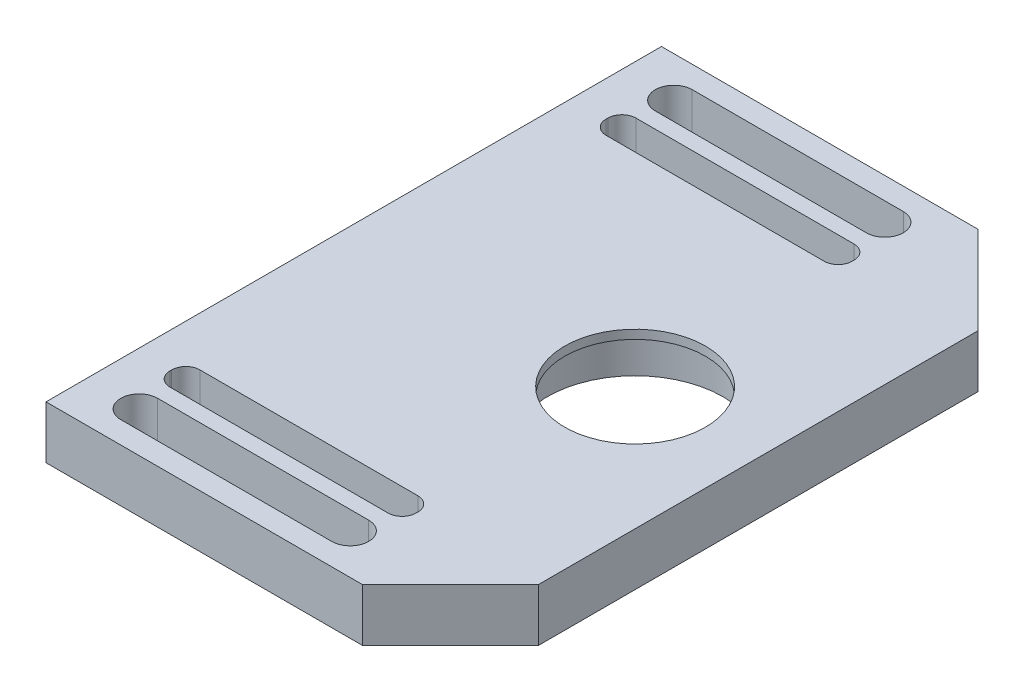
SolidWorks part; units mm, degrees
material "1060 Legierung"
ref_plane "Ebene vorne" through (0, 0, 0) normal (0, 0, 1) x (1, 0, 0)
ref_plane "Ebene oben" through (0, 0, 0) normal (0, 1, 0) x (1, 0, 0)
ref_plane "Ebene rechts" through (0, 0, 0) normal (1, 0, 0) x (0, 0, -1)
sketch "Skizze1" plane through (0, 0, 0) normal (0, 1, 0) x (1, 0, 0)
  line L0 (-9, 0) -> (9, 0) construction
  line L1 (-9, 17.5) -> (9, 17.5)
  line L2 (-9, 17.5) -> (-9, -17.5)
  line L3 (-6, -15.2) -> (6, -15.2) construction
  line L4 (-6, -16.25) -> (6, -16.25)
  line L5 (-6, -14.15) -> (6, -14.15)
  line L6 (-7, 13.25) -> (7, 13.25)
  line L7 (-7, 13.25) -> (-7, 11.55)
  line L8 (-7, 11.55) -> (7, 11.55)
  line L9 (7, 13.25) -> (7, 11.55)
  line L10 (-6, 15.2) -> (6, 15.2) construction
  line L11 (-6, 16.25) -> (6, 16.25)
  line L12 (-6, 14.15) -> (6, 14.15)
  line L13 (0, 0) -> (0, 13.25) construction
  line L14 (0, 15.2) -> (0, 0) construction
  line L15 (7, -13.25) -> (7, -11.55)
  line L16 (-7, -11.55) -> (7, -11.55)
  line L17 (-7, -13.25) -> (-7, -11.55)
  line L18 (-7, -13.25) -> (7, -13.25)
  line L19 (-9, -17.5) -> (9, -17.5)
  line L20 (9, -17.5) -> (14, -12.5)
  line L21 (14, -12.5) -> (14, 12.5)
  line L22 (14, 12.5) -> (9, 17.5)
  line L23 (9, 17.5) -> (9, -17.5) construction
  line L24 (9, 0) -> (14, 0) construction
  arc A0 (-6, 16.25) -> (-6, 14.15) centre (-6, 15.2) ccw
  arc A1 (6, 14.15) -> (6, 16.25) centre (6, 15.2) ccw
  arc A2 (-6, -16.25) -> (-6, -14.15) centre (-6, -15.2) cw
  arc A3 (6, -14.15) -> (6, -16.25) centre (6, -15.2) cw
  point P14 (0, 15.2)
  point P19 (0, -15.2)
  dimension "D5" = 35
  dimension "D6" = 12
  dimension "D7" = 1.05
  dimension "D8" = 30.4
  dimension "D9" = 45
  dimension "D1" = 18
  dimension "D2" = 14
  dimension "D3" = 1.7
  dimension "D4" = 26.5
  dimension "D10" = 23
extrude "Aufsatz-Linear austragen1" add sketch "Skizze1" against normal mid plane 3
fillet "Verrundung1" radius 0.8 8 edges at (7, 0, -13.25) (7, 0, -11.55) (-7, 0, -11.55) (-7, 0, -13.25) (7, 0, 13.25) (7, 0, 11.55) (-7, 0, 13.25) (-7, 0, 11.55)
sketch "Skizze3" plane through (0, 0, 0) normal (0, 0, 1) x (1, 0, 0)
  line L0 (7, 9.8285) -> (7, -9.5913) construction
  line L2 (-9, -1.5) -> (-9, 1.5) construction
  line L3 (5, -1.7017) -> (7, -0.5)
  line L5 (7, -0.5) -> (7, -11.7017)
  line L6 (7, -11.7017) -> (5, -11.7017)
  line L7 (5, -11.7017) -> (5, -1.7017)
  line L8 (5, -1.7017) -> (5.9524, -0.2665)
  line L9 (-9, -1.5) -> (9, -1.5) construction
  dimension "D1" = 16
  dimension "D2" = 59
  dimension "D3" = 1
  dimension "D4" = 10
  dimension "D5" = 4
revolve "Schnitt-Rotation2" [suppressed] cut sketch "Skizze3" angle 360 about L0
sketch "Skizze4" plane through (0, -1.5, 0) normal (0, -1, 0) x (1, 0, 0)
  line L0 (-9, -17.5) -> (-9, 17.5) construction
  line L1 (7, 0) -> (-9, 0) construction
  circle A0 centre (7, 0) radius 5
  circle A1 centre (7, 0) radius 4
  dimension "D1" = 10
  dimension "D2" = 8
  dimension "D3" = 16
extrude "Schnitt-Linear austragen1" cut sketch "Skizze4" against normal offset from surface (2.5 mm away) 0.5 contours A0 up to face at (0, 1.5, 12.4)
extrude "Schnitt-Linear austragen2" cut sketch "Skizze4<3>" against normal through all contours A1
sketch "Skizze4<3>" plane through (0, -1.5, 0) normal (0, -1, 0) x (1, 0, 0) same geometry as "Skizze4"
